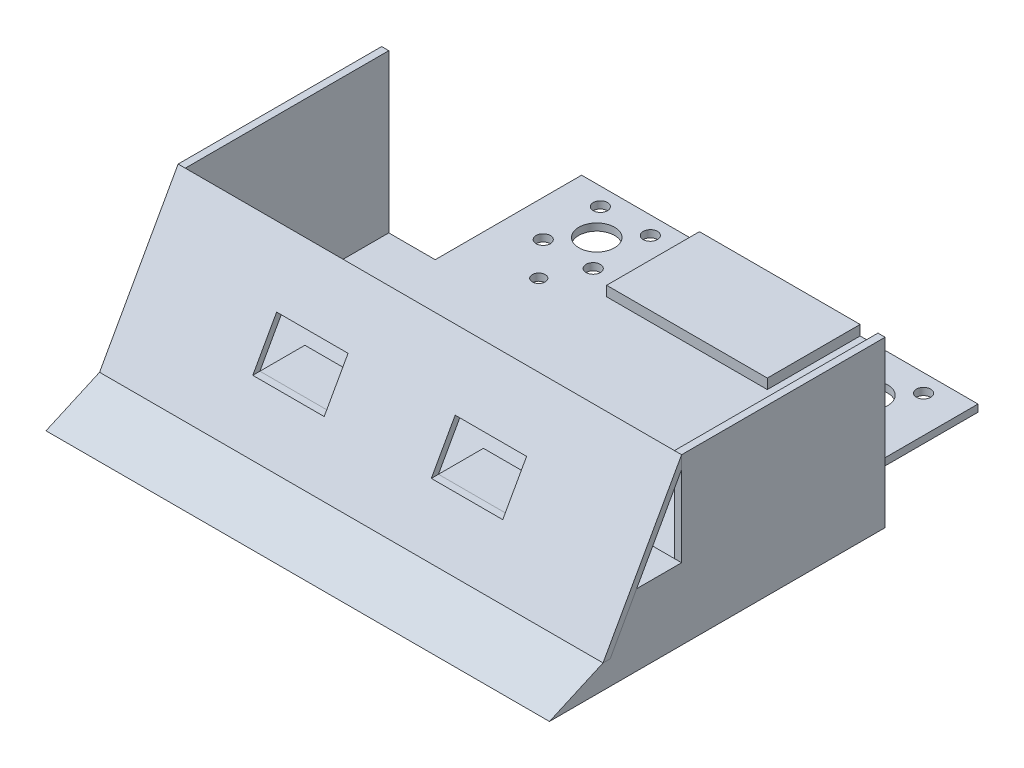
SolidWorks part; units mm, degrees
note: The reader was unsure of these and kept them because the rebuilt part matched: shared geometry of "Sketch2<9>", "Sketch2<15>", "Sketch2<17>", "Sketch2<18>", "Sketch13<3>", "Sketch2<22>".
ref_plane "Front Plane" through (0, 0, 0) normal (0, 0, 1) x (1, 0, 0)
ref_plane "Top Plane" through (0, 0, 0) normal (0, 1, 0) x (1, 0, 0)
ref_plane "Right Plane" through (0, 0, 0) normal (1, 0, 0) x (0, 0, -1)
sketch "Sketch1" plane through (0, 0, 0) normal (0, 1, 0) x (1, 0, 0)
  line L0 (-55.5, 0) -> (55.5098, 0)
  line L18 (-70.5, -120) -> (70.5, -120)
  line L19 (-55.5, 0) -> (-55.5, -41)
  line L21 (-70.5, -41) -> (-55.5, -41)
  line L22 (70.5, -41) -> (55.5098, -41)
  line L23 (55.5098, -41) -> (55.5098, 0)
  line L25 (-70.5, -41) -> (-70.5, -120)
  line L27 (70.5, -41) -> (70.5, -120)
  circle A25 centre (-36.5, -90.0239) radius 1.8
  circle A26 centre (36.5, -31) radius 1.8
  circle A27 centre (36.5, -90.0239) radius 1.8
  circle A28 centre (-36.5, -31) radius 1.8
  circle A50 centre (-45.25, -21) radius 2
  circle A51 centre (-31.25, -21) radius 2
  circle A52 centre (-31.25, -5) radius 2
  circle A53 centre (-45.25, -5) radius 2
  circle A54 centre (-38.2682, -13) radius 5
  circle A55 centre (31.2598, -21) radius 2
  circle A56 centre (45.2598, -21) radius 2
  circle A57 centre (45.2598, -5) radius 2
  circle A58 centre (31.2598, -5) radius 2
  circle A59 centre (38.25, -13) radius 5
extrude "Boss-Extrude1" add sketch "Sketch1" along normal blind 2
sketch "Sketch2" plane through (0, 0, 0) normal (1, 0, 0) x (0, 0, -1)
  line L12 (-98, 0) -> (-98, 2)
  line L16 (-98, 20) -> (-110.5926, 20)
  line L23 (-120, 6.6987) -> (-112.5926, 20)
  line L25 (-120, 2) -> (-98, 2)
  line L26 (-120, 6.6987) -> (-120, 2)
  line L27 (-120, 0) -> (-120, 2)
  line L28 (-118, 0) -> (-98, 0)
  line L29 (-118, 6.6987) -> (-98, 6.6987)
  line L30 (-98, 6.6987) -> (-98, 20)
  line L31 (-98, 2) -> (-98, 6.6987)
  line L32 (-118, 0) -> (-120, 0)
  line L33 (-118, 0) -> (-118, 6.6987)
  line L34 (-110.5926, 20) -> (-112.5926, 20)
  line L35 (-110.5926, 20) -> (-118, 6.6987)
  line L36 (-118, 6.6987) -> (-120, 6.6987)
  line L37 (-120, 0) -> (-135, 0)
  line L38 (-135, 0) -> (-120, 6.6987)
sketch "Sketch7" plane through (0, 0, 0) normal (0, 1, 0) x (1, 0, 0)
  circle A4 centre (-47.9984, -104.6306) radius 5
  circle A5 centre (48, -105.0056) radius 5
extrude "Boss-Extrude6" add sketch "Sketch2<9>" along normal blind 70.5 and the other way blind 70.5 contours L26 L25 L31 L30 L16 L34 L23
sketch "Sketch2<9>" plane through (0, 0, 0) normal (1, 0, 0) x (0, 0, -1) same geometry as "Sketch2"
extrude "Cut-Extrude8" cut sketch "Sketch2<15>" against normal blind 15 and the other way blind 15 contours L23 L34 L16 L30 L29 L36
sketch "Sketch2<15>" plane through (0, 0, 0) normal (1, 0, 0) x (0, 0, -1) same geometry as "Sketch2"
extrude "Cut-Extrude9" cut sketch "Sketch2<17>" against normal blind 25 from offset 35 contours L29 L30 L16 L34 L23 L36 offset against normal yes
sketch "Sketch2<17>" plane through (0, 0, 0) normal (1, 0, 0) x (0, 0, -1) same geometry as "Sketch2"
extrude "Cut-Extrude10" cut sketch "Sketch2<18>" along normal blind 25 from offset 35 contours L29 L30 L16 L34 L23 L36
sketch "Sketch2<18>" plane through (0, 0, 0) normal (1, 0, 0) x (0, 0, -1) same geometry as "Sketch2"
extrude "Cut-Extrude11" cut sketch "Sketch2" against normal blind 70.5 and the other way blind 70.5 contours L36 L23 L34 L35
sketch "Sketch11" plane through (0, 0, 0) normal (0, 0, 1) x (1, 0, 0)
  line L0 (-35, 2) -> (-60, 2)
  line L3 (-60, 2) -> (-60, 6.6987)
  line L11 (-60, 6.6987) -> (-35, 6.6987)
  line L12 (-35, 6.6987) -> (-35, 2)
  line L13 (35, 6.6987) -> (60, 6.6987)
  line L14 (60, 6.6987) -> (60, 2)
  line L15 (60, 2) -> (35, 2)
  line L16 (35, 2) -> (35, 6.6987)
extrude "Cut-Extrude12" cut sketch "Sketch11" against normal blind 20 from offset 115
extrude "Cut-Extrude13" cut sketch "Sketch7" against normal blind 10 from offset 4
sketch "Sketch12" plane through (0, 0, 0) normal (1, 0, 0) x (0, 0, -1)
  line L0 (-98, 42.6078) -> (-98, 46.1987)
  line L1 (-120, 6.6987) -> (-118, 6.6987)
  line L6 (-120, 6.6987) -> (-98, 46.1987)
  line L7 (-118, 6.6987) -> (-98, 42.6078)
extrude "Boss-Extrude7" add sketch "Sketch12" along normal blind 70.5 and the other way blind 70.5 separate body
sketch "Sketch13" plane through (0, 0, 0) normal (1, 0, 0) x (0, 0, -1)
  line L0 (-112.5926, 20) -> (-112.5926, 32)
  line L1 (-112.5926, 20) -> (-98, 20)
  line L2 (-98, 20) -> (-98, 32)
  line L3 (-98, 32) -> (-112.5926, 32)
sketch "Sketch15" plane through (0, 0, 0) normal (0, 1, 0) x (1, 0, 0)
  line L0 (-70.5, -98) -> (-70.5, -41)
  line L1 (-70.5, -41) -> (-68.5, -41)
  line L2 (-55.5, -41) -> (-70.5, -41) construction
  line L4 (-70.5, -98) -> (70.5, -98) construction
  line L5 (-68.5, -98) -> (-70.5, -98)
  line L6 (70.5, -98) -> (70.5, -41)
  line L7 (70.5, -41) -> (68.5, -41)
  line L8 (70.5, -41) -> (55.5098, -41) construction
  line L10 (68.5, -98) -> (70.5, -98)
  line L17 (-68.5, -98) -> (-68.5, -41)
  line L18 (68.5, -98) -> (68.5, -41)
extrude "Boss-Extrude8" add sketch "Sketch15" along normal blind 46.2
extrude "Cut-Extrude16" cut sketch "Sketch13" against normal blind 20 from offset 15 offset against normal yes
extrude "Cut-Extrude17" cut sketch "Sketch13<3>" along normal blind 20 from offset 15
sketch "Sketch13<3>" plane through (0, 0, 0) normal (1, 0, 0) x (0, 0, -1) same geometry as "Sketch13"
other "Save Bodies2"
sketch "Sketch17" plane through (0, 0, 0) normal (0, 1, 0) x (1, 0, 0)
  line L0 (0.0049, 0) -> (22.5049, 0)
  line L1 (55.5098, 0) -> (-55.5, 0) construction
  line L2 (22.5049, 0) -> (22.5049, -26)
  line L3 (0.0049, 0) -> (-22.4951, 0)
  line L4 (-22.4951, 0) -> (-22.4951, -26)
  line L5 (-22.4951, -26) -> (22.5049, -26)
extrude "Boss-Extrude9" add sketch "Sketch17" along normal blind 4.8
extrude "Boss-Extrude10" add sketch "Sketch2<22>" along normal blind 70.5 and the other way blind 70.5 contours L37 L38 L26 L27
sketch "Sketch2<22>" plane through (0, 0, 0) normal (1, 0, 0) x (0, 0, -1) same geometry as "Sketch2"
